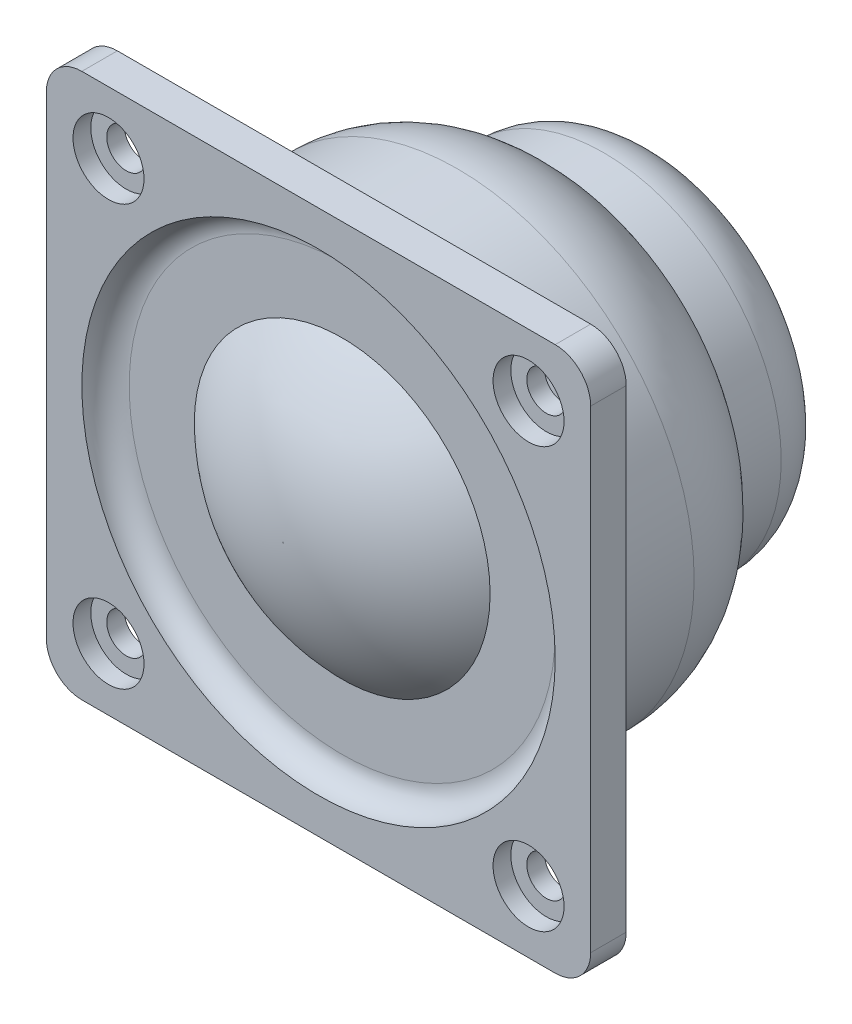
SolidWorks part; units mm, degrees
ref_plane "Plan de face" through (0, 0, 0) normal (0, 0, 1) x (1, 0, 0)
ref_plane "Plan de dessus" through (0, 0, 0) normal (0, 1, 0) x (1, 0, 0)
ref_plane "Plan de droite" through (0, 0, 0) normal (1, 0, 0) x (0, 0, -1)
sketch "Esquisse1" plane through (0, 0, 0) normal (0, 0, 1) x (1, 0, 0)
  line L0 (23, -23) -> (-23, 23) construction
  line L1 (-20, 23) -> (20, 23)
  line L2 (-23, 20) -> (-23, -20)
  line L3 (-20, -23) -> (20, -23)
  line L4 (23, 20) -> (23, -20)
  line L5 (17.7484, 17.7484) -> (-17.7484, -17.7484) construction
  arc A0 (-23, -20) -> (-20, -23) centre (-20, -20) ccw
  arc A1 (20, -23) -> (23, -20) centre (20, -20) ccw
  arc A2 (20, 23) -> (23, 20) centre (20, 20) cw
  arc A3 (-20, 23) -> (-23, 20) centre (-20, 20) ccw
  circle A4 centre (0, 0) radius 25.1 construction
  circle A5 centre (17.7484, 17.7484) radius 1.65
  circle A6 centre (-17.7484, 17.7484) radius 1.65
  circle A7 centre (17.7484, -17.7484) radius 1.65
  circle A8 centre (-17.7484, -17.7484) radius 1.65
  dimension "D1" = 3
  dimension "D2" = 50.2
  dimension "D3" = 3.3
extrude "Boss.-Extru.1" add sketch "Esquisse1" along normal blind 3
sketch "Esquisse2" plane through (0, 0, 3) normal (0, 0, 1) x (1, 0, 0)
  circle A0 centre (-17.7484, 17.7484) radius 3
  circle A1 centre (17.7484, 17.7484) radius 3
  circle A2 centre (17.7484, -17.7484) radius 3
  circle A3 centre (-17.7484, -17.7484) radius 3
  dimension "D1" = 6
extrude "Enlèv. mat.-Extru.1" cut sketch "Esquisse2" against normal blind 1.5
sketch "Esquisse3" plane through (0, 0, 0) normal (0, 0, -1) x (-1, 0, 0)
  circle A0 centre (0, 0) radius 20
  dimension "D1" = 40
extrude "Boss.-Extru.2" add sketch "Esquisse3" along normal blind 17.4
sketch "Esquisse4" plane through (0, 0, -17.4) normal (0, 0, -1) x (-1, 0, 0)
  circle A0 centre (0, 0) radius 15
  dimension "D1" = 30
extrude "Boss.-Extru.3" add sketch "Esquisse4" along normal blind 8.7
fillet "Congé1" radius 10 1 edges at (-20, 0, -17.4)
fillet "Congé2" radius 5 1 edges at (-15, 0, -26.1)
sketch "Esquisse5" plane through (0, 0, 3) normal (0, 0, 1) x (1, 0, 0)
  circle A0 centre (0, 0) radius 20
  dimension "D1" = 40
extrude "Enlèv. mat.-Extru.2" cut sketch "Esquisse5" against normal blind 2
sketch "Esquisse6" plane through (0, 0, 1) normal (0, 0, 1) x (1, 0, 0)
  circle A0 centre (0, 0) radius 12.5
  dimension "D1" = 25
extrude "Boss.-Extru.4" add sketch "Esquisse6" along normal blind 5
fillet "Congé3" radius 18 1 edges at (12.5, 0, 6)
fillet "Congé4" radius 2 1 edges at (20, 0, 1)
